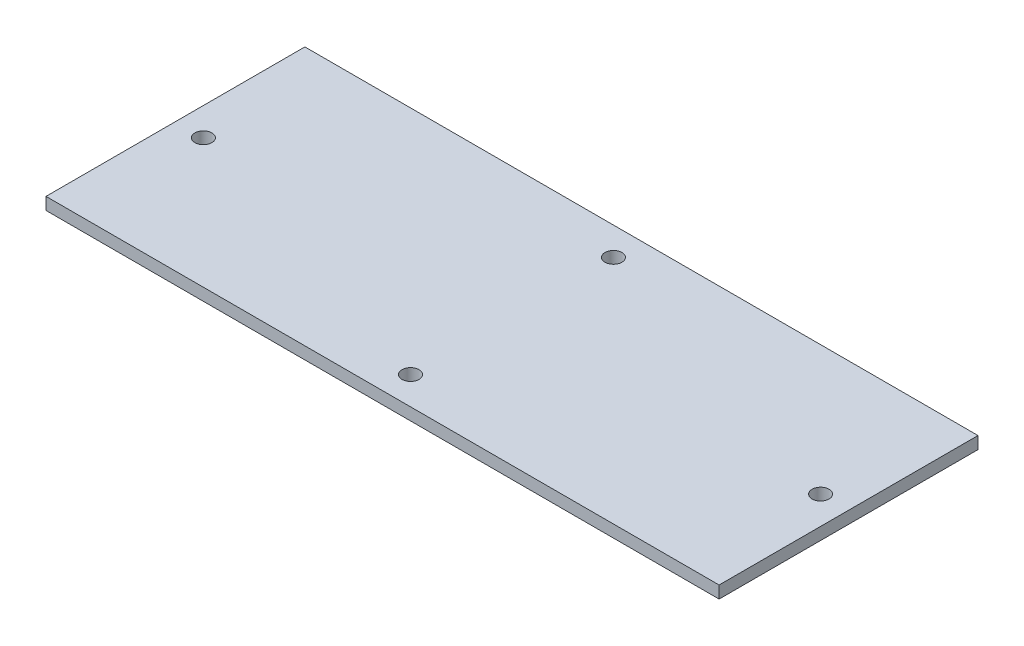
SolidWorks part; units mm, degrees
material "Thornel VCB-20 Carbon Cloth"
ref_plane "Front Plane" through (0, 0, 0) normal (0, 0, 1) x (1, 0, 0)
ref_plane "Top Plane" through (0, 0, 0) normal (0, 1, 0) x (1, 0, 0)
ref_plane "Right Plane" through (0, 0, 0) normal (1, 0, 0) x (0, 0, -1)
sketch "Sketch1" plane through (0, 0, 0) normal (0, 1, 0) x (1, 0, 0)
  line L1 (-82.55, -31.75) -> (82.55, -31.75)
  line L2 (-82.55, -31.75) -> (-82.55, 31.75)
  line L3 (-82.55, 31.75) -> (82.55, 31.75)
  line L4 (82.55, -31.75) -> (82.55, 31.75)
  dimension "D1" = 63.5
  dimension "D2" = 165.1
  dimension "D3" = 31.75
  dimension "D4" = 82.55
extrude "Boss-Extrude1" add sketch "Sketch1" along normal blind 3
sketch "Sketch2" plane through (0, 3, 0) normal (0, 1, 0) x (1, 0, 0)
  line L0 (-82.55, 31.75) -> (-82.55, -31.75) construction
  line L1 (82.55, -31.75) -> (82.55, 31.75) construction
  line L2 (82.55, 31.75) -> (-82.55, 31.75) construction
  line L3 (-82.55, -31.75) -> (82.55, -31.75) construction
  circle A0 centre (-77.47, 26.67) radius 1.5
  circle A1 centre (-77.47, -26.67) radius 1.5
  circle A2 centre (77.47, 26.67) radius 1.5
  circle A3 centre (77.47, -26.67) radius 1.5
  dimension "D1" = 3
  dimension "D2" = 3
  dimension "D3" = 3
  dimension "D4" = 3
  dimension "D5" = 5.08
  dimension "D6" = 5.08
  dimension "D7" = 5.08
  dimension "D8" = 5.08
  dimension "D9" = 5.08
  dimension "D10" = 5.08
  dimension "D11" = 5.08
  dimension "D12" = 5.08
sketch "Sketch3" plane through (0, 3, 0) normal (0, 1, 0) x (1, 0, 0)
  line L0 (-82.55, 31.75) -> (-82.55, -31.75) construction
  line L1 (82.55, -31.75) -> (82.55, 31.75) construction
  line L2 (-82.55, -31.75) -> (82.55, -31.75) construction
  line L3 (82.55, 31.75) -> (-82.55, 31.75) construction
  circle A0 centre (-75.692, 0) radius 2.0828
  circle A1 centre (75.692, 0) radius 2.0828
  circle A2 centre (0, -24.892) radius 2.0828
  circle A3 centre (0, 24.892) radius 2.0828
  dimension "D1" = 6.858
  dimension "D2" = 6.858
  dimension "D3" = 6.858
  dimension "D4" = 6.858
extrude "Cut-Extrude2" cut sketch "Sketch3" against normal blind 5.08
